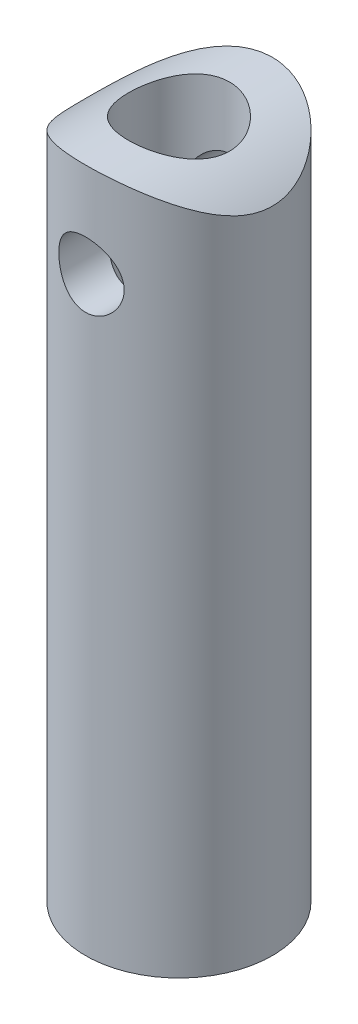
SolidWorks part; units mm, degrees
ref_plane "Front Plane" through (0, 0, 0) normal (0, 0, 1) x (1, 0, 0)
ref_plane "Top Plane" through (0, 0, 0) normal (0, 1, 0) x (1, 0, 0)
ref_plane "Right Plane" through (0, 0, 0) normal (1, 0, 0) x (0, 0, -1)
sketch "Sketch1" plane through (0, 0, 0) normal (0, 0, 1) x (1, 0, 0)
  line L0 (2.15, 0) -> (6, 0)
  line L1 (6, 0) -> (6, 44)
  line L2 (6, 44) -> (3.25, 44)
  line L4 (2.15, 10) -> (3.25, 10)
  line L5 (3.25, 10) -> (3.25, 44)
  line L6 (2.15, 10) -> (2.15, 0)
  line L7 (0, 0) -> (0, 45.7185) construction
  dimension "D1" = 6
  dimension "D2" = 2.15
  dimension "D3" = 3.25
  dimension "D4" = 10
  dimension "D5" = 34
revolve "Revolve1" add sketch "Sketch1" angle 360 about L7
sketch "Sketch2" plane through (0, 0, 0) normal (0, 0, 1) x (1, 0, 0)
  line L0 (0, 44) -> (0, 40) construction
  line L1 (6, 44) -> (-6, 44) construction
  line L2 (-6, 41.7082) -> (-6, 44)
  line L3 (-6, 44) -> (6, 44)
  line L4 (6, 44) -> (6, 41.7082)
  circle A0 centre (0, 37.9) radius 2.1
  arc A1 (6, 41.7082) -> (-6, 41.7082) centre (0, 35) ccw
  dimension "D1" = 4.2
  dimension "D3" = 9
  dimension "D2" = 4
extrude "Cut-Extrude1" cut sketch "Sketch2" against normal blind 10 and the other way blind 10 contours A0 | A1 L4 L3 | A1 L3 L2 region at (4.5409, 43.3306, 0) region at (-4.5409, 43.3306, 0) region at (0, 37.9, 0)
